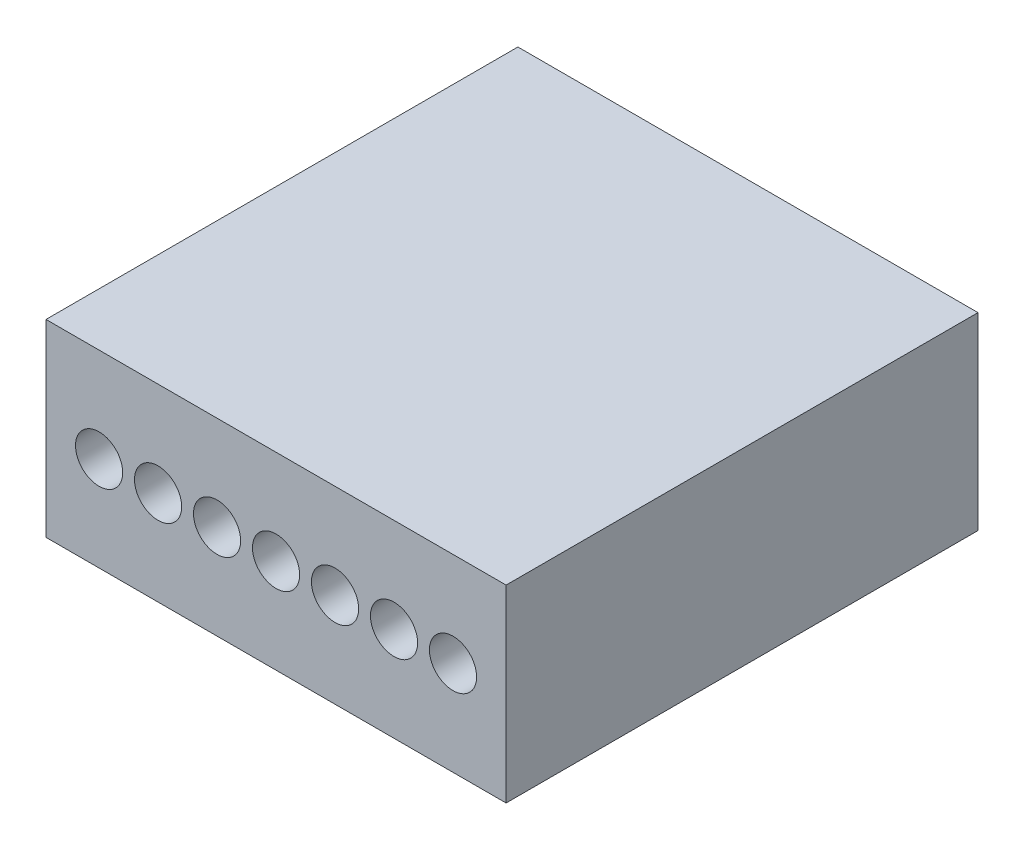
SolidWorks part; units mm, degrees
ref_plane "Front Plane" through (0, 0, 0) normal (0, 0, 1) x (1, 0, 0)
ref_plane "Top Plane" through (0, 0, 0) normal (0, 1, 0) x (1, 0, 0)
ref_plane "Right Plane" through (0, 0, 0) normal (1, 0, 0) x (0, 0, -1)
sketch "Sketch2" plane through (0, 0, 0) normal (0, 0, 1) x (1, 0, 0)
  line L1 (0, 0) -> (9.75, 0)
  line L2 (0, 0) -> (0, 4)
  line L3 (0, 4) -> (9.75, 4)
  line L4 (9.75, 0) -> (9.75, 4)
  dimension "D1" = 9.75
  dimension "D2" = 4
extrude "Boss-Extrude1" add sketch "Sketch2" along normal blind 10
sketch "Sketch3" plane through (0, 0, 10) normal (0, 0, 1) x (1, 0, 0)
  line L0 (0, 2) -> (9.75, 2) construction
  line L1 (0, 4) -> (0, 0) construction
  line L2 (9.75, 0) -> (9.75, 4) construction
  line L3 (0, 2) -> (9.75, 2) construction
  line L4 (9.75, 4) -> (0, 4) construction
  line L5 (0, 0) -> (9.75, 0) construction
  line L6 (1.125, 4) -> (1.125, 0) construction
  circle A0 centre (1.125, 2) radius 0.5
  circle A1 centre (2.375, 2) radius 0.5
  circle A2 centre (3.625, 2) radius 0.5
  circle A3 centre (4.875, 2) radius 0.5
  circle A4 centre (6.125, 2) radius 0.5
  circle A5 centre (7.375, 2) radius 0.5
  circle A6 centre (8.625, 2) radius 0.5
  circle A21 centre (24.875, 2) radius 0.5 [skipped]
  circle A22 centre (23.625, 2) radius 0.5 [skipped]
  circle A23 centre (22.375, 2) radius 0.5 [skipped]
  circle A24 centre (21.125, 2) radius 0.5 [skipped]
  circle A25 centre (19.875, 2) radius 0.5 [skipped]
  circle A26 centre (18.625, 2) radius 0.5 [skipped]
  circle A27 centre (17.375, 2) radius 0.5 [skipped]
  circle A28 centre (16.125, 2) radius 0.5 [skipped]
  circle A29 centre (14.875, 2) radius 0.5 [skipped]
  circle A30 centre (13.625, 2) radius 0.5 [skipped]
  circle A31 centre (12.375, 2) radius 0.5 [skipped]
  circle A32 centre (11.125, 2) radius 0.5 [skipped]
  circle A33 centre (9.875, 2) radius 0.5 [skipped]
  dimension "D1" = 1
  dimension "D2" = 2
  dimension "D3" = 1.125
  dimension "D5" = 1.25
  dimension "D4" = 20
extrude "Cut-Extrude1" cut sketch "Sketch3" against normal blind 5
sketch "Sketch4" plane through (0, 0, 10) normal (0, 0, 1) x (1, 0, 0)
  point P0 (1.125, 2)
  point P1 (2.375, 2)
  point P3 (3.625, 2)
  point P5 (4.875, 2)
  point P7 (6.125, 2)
  point P9 (7.375, 2)
  point P11 (8.625, 2)
other "CPoint1" parameters "Diameter"=25.4, "StubLength"=38.1
ref_axis "Axis1" through (1.125, 2, 20) along (0, 0, -1)
other "CPoint2" parameters "Diameter"=25.4, "StubLength"=38.1
ref_axis "Axis2" through (2.375, 2, 20) along (0, 0, -1)
other "CPoint3" parameters "Diameter"=25.4, "StubLength"=38.1
ref_axis "Axis3" through (3.625, 2, 20) along (0, 0, -1)
other "CPoint4" parameters "Diameter"=25.4, "StubLength"=38.1
ref_axis "Axis4" through (4.875, 2, 20) along (0, 0, -1)
other "CPoint5" parameters "Diameter"=25.4, "StubLength"=38.1
ref_axis "Axis5" through (6.125, 2, 20) along (0, 0, -1)
other "CPoint6" parameters "Diameter"=25.4, "StubLength"=38.1
ref_axis "Axis6" through (7.375, 2, 20) along (0, 0, -1)
other "CPoint7" parameters "Diameter"=25.4, "StubLength"=38.1
ref_axis "Axis7" through (8.625, 2, 20) along (0, 0, -1)
